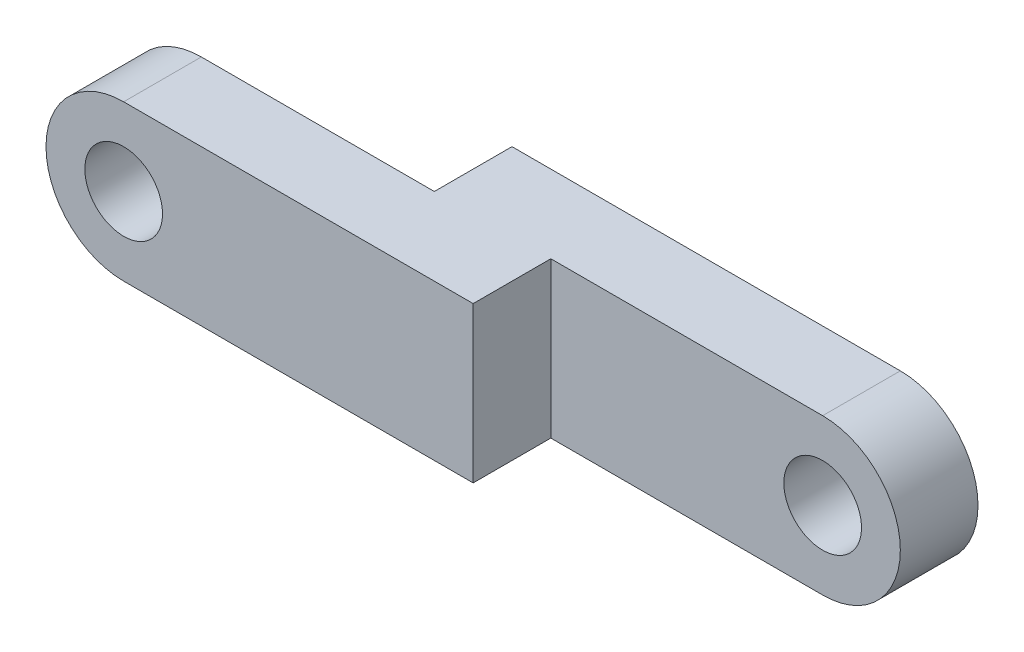
SolidWorks part; units mm, degrees
ref_plane "Front Plane" through (0, 0, 0) normal (0, 0, 1) x (1, 0, 0)
ref_plane "Top Plane" through (0, 0, 0) normal (0, 1, 0) x (1, 0, 0)
ref_plane "Right Plane" through (0, 0, 0) normal (1, 0, 0) x (0, 0, -1)
sketch "Sketch1" plane through (0, 0, 0) normal (0, 0, 1) x (1, 0, 0)
  line L0 (-10.16, 0) -> (10.16, 0) construction
  line L1 (-10.16, 2.54) -> (10.16, 2.54)
  line L2 (-10.16, -2.54) -> (10.16, -2.54)
  arc A0 (-10.16, 2.54) -> (-10.16, -2.54) centre (-10.16, 0) ccw
  arc A1 (10.16, -2.54) -> (10.16, 2.54) centre (10.16, 0) ccw
  circle A2 centre (-10.16, 0) radius 1.27
  circle A3 centre (10.16, 0) radius 1.27
  point P2 (0, 0)
  dimension "D2" = 2.54
  dimension "D3" = 2.54
  dimension "D1" = 20.32
extrude "Boss-Extrude1" add sketch "Sketch1" along normal blind 1.27 and the other way blind 1.27
sketch "Sketch3" plane through (0, 0, -1.27) normal (0, 0, -1) x (-1, 0, 0)
  line L0 (2.54, 2.54) -> (2.54, -2.54)
  line L2 (10.16, 2.54) -> (-10.16, 2.54)
  line L3 (-10.16, -2.54) -> (10.16, -2.54)
  line L4 (10.16, 2.54) -> (-10.16, 2.54)
  line L5 (-10.16, -2.54) -> (10.16, -2.54)
  circle A0 centre (-10.16, 0) radius 1.27 construction
  circle A1 centre (-10.16, 0) radius 1.27
  arc A2 (10.16, -2.54) -> (10.16, 2.54) centre (10.16, 0) ccw
  arc A3 (-10.16, 2.54) -> (-10.16, -2.54) centre (-10.16, 0) ccw
  arc A4 (10.16, -2.54) -> (10.16, 2.54) centre (10.16, 0) ccw
  arc A5 (-10.16, 2.54) -> (-10.16, -2.54) centre (-10.16, 0) ccw
  circle M5 centre (-10.16, 0) radius 1.27
  line M8 (10.16, 2.54) -> (-10.16, 2.54)
  arc M9 (-10.16, 2.54) -> (-10.16, -2.54) centre (-10.16, 0) ccw
  line M10 (-10.16, -2.54) -> (10.16, -2.54)
  dimension "D2" = 12.7
  dimension "D1" = 0
extrude "Boss-Extrude2" add sketch "Sketch3" along normal blind 2.54 contours L0 M8 M9 M10 M5 region at (4.4294, 0, -1.27)
mirror "Mirror1" [suppressed] about plane through (0, 0, 0) normal (0, 0, 1)
sketch "Sketch4" plane through (0, 2.54, 0) normal (0, 1, 0) x (1, 0, 0)
  line L0 (1.27, 1.27) -> (1.27, -1.27)
  line L1 (1.27, 1.27) -> (12.7, 1.27)
  line L2 (1.27, -1.27) -> (12.7, -1.27)
  line L3 (12.7, 1.27) -> (12.7, -1.27)
  line L5 (12.7, -1.27) -> (12.7, 3.81) construction
  line L6 (10.16, -1.27) -> (-10.16, -1.27) construction
  line L7 (-2.54, 1.27) -> (-10.16, 1.27) construction
  line L8 (-2.54, 3.81) -> (-2.54, 1.27) construction
  point P0 (-2.54, 2.54)
  dimension "D1" = 3.81
extrude "Cut-Extrude2" cut sketch "Sketch4" against normal through all
